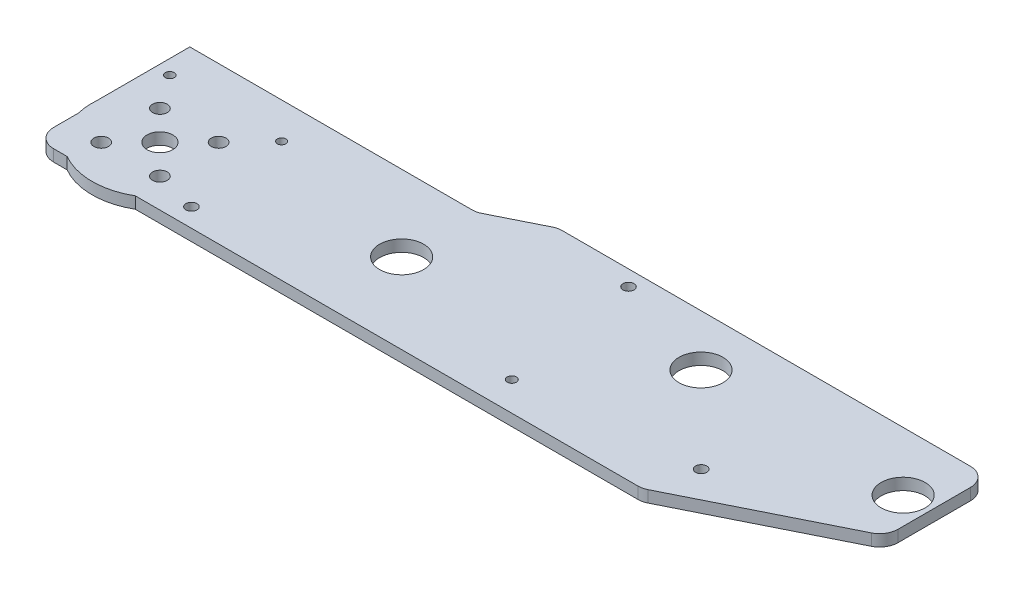
SolidWorks part; units mm, degrees
ref_plane "Front" through (0, 0, 0) normal (0, 0, 1) x (1, 0, 0)
ref_plane "Top" through (0, 0, 0) normal (0, 1, 0) x (1, 0, 0)
ref_plane "Right" through (0, 0, 0) normal (1, 0, 0) x (0, 0, -1)
sketch "Sketch1" plane through (0, 0, 0) normal (0, 1, 0) x (1, 0, 0)
  line L1 (0, 0) -> (210, 0)
  line L2 (0, 0) -> (0, -50)
  line L3 (0, -50) -> (210, -50)
  line L4 (210, 0) -> (210, -50)
  circle A7 centre (3.4895, -16.7877) radius 1.2117
  circle A8 centre (34.3726, -17.194) radius 1.1656
  circle A9 centre (37.5207, -44.9212) radius 1.5
  circle A10 centre (122, -42.0581) radius 1.25
  circle A12 centre (168.9752, -37.4032) radius 1.5173
  circle A13 centre (78.0103, -28.1) radius 3.4
  dimension "D1" = 210
  dimension "D2" = 50
extrude "Boss-Extrude1" add sketch "Sketch1" along normal blind 3.175
sketch "Sketch2" plane through (0, 3.175, 0) normal (0, 1, 0) x (1, 0, 0)
  line L0 (210, 0) -> (0, 0) construction
  line L1 (0, 0) -> (0, -50) construction
  circle A0 centre (10, -26) radius 2
  circle A1 centre (10, -42) radius 2
  circle A2 centre (26, -26) radius 2
  circle A3 centre (26, -42) radius 2
  dimension "D1" = 16
  dimension "D2" = 16
  dimension "D3" = 16
  dimension "D4" = 26
  dimension "D5" = 10
  dimension "D6" = 10
  dimension "D7" = 26
  dimension "D8" = 16
extrude "Cut-Extrude1" cut sketch "Sketch2" against normal blind 10
sketch "Sketch3" plane through (0, 3.175, 0) normal (0, 1, 0) x (1, 0, 0)
  line L0 (210, 0) -> (0, 0) construction
  line L1 (210, 0) -> (0, 0) construction
  circle A0 centre (78.0103, -28.1) radius 6
  circle A1 centre (145.5313, -14) radius 6
  circle A2 centre (18, -34) radius 0.587
  circle A3 centre (26, -26) radius 2 construction
  circle A4 centre (202.6463, -16) radius 6
  dimension "D1" = 28.1
  dimension "D3" = 16
  dimension "D4" = 14
  dimension "D7" = 125.222
  dimension "D2" = 60.2996
  dimension "D5" = 8
  dimension "D6" = 8
  dimension "D8" = 57.15
extrude "Cut-Extrude2" cut sketch "Sketch3" against normal blind 57.15
sketch "Sketch4" [suppressed] plane through (0, 3.175, 0) normal (0, 1, 0) x (1, 0, 0)
  line L0 (3.4895, -16.7877) -> (18, -34)
  line L1 (3.4895, -20.6627) -> (5.9498, -23.5811)
  line L2 (18, -34) -> (34.3726, -17.194)
  line L3 (34.3726, -17.194) -> (75.8499, -28.1)
  line L4 (75.8499, -28.1) -> (37.5207, -44.9212)
  line L5 (7.3432, -17.194) -> (9.8664, -20.303)
  circle A0 centre (18, -34) radius 15.9299
  circle A1 centre (3.4895, -16.7877) radius 3.8751
  circle A2 centre (34.3726, -17.194) radius 3.7227
  circle A3 centre (37.5207, -44.9212) radius 3.8676
  circle A4 centre (75.8499, -28.1) radius 12.797
  circle A5 centre (112.3021, -4.7393) radius 5.1588
  circle A6 centre (118.879, -40.0177) radius 4.9035
  circle A7 centre (140.772, -16) radius 12.6375
  circle A8 centre (168.9752, -37.4032) radius 4.2066
  circle A9 centre (197.922, -16) radius 12.8
sketch "Sketch5" [suppressed] plane through (0, 3.175, 0) normal (0, 1, 0) x (1, 0, 0)
  line L0 (210, 0) -> (0, 0) construction
  line L2 (-0.6266, -16.7877) -> (37.5207, -16.7877)
  line L3 (-0.6266, -16.7877) -> (-0.6266, -44.9212)
  line L4 (-0.6266, -44.9212) -> (37.5207, -44.9212)
  line L5 (37.5207, -16.7877) -> (37.5207, -44.9212)
  line L6 (75.8499, -15.182) -> (37.5207, -15.182)
  line L7 (75.8499, -15.182) -> (75.8499, -44.9212)
  line L8 (75.8499, -44.9212) -> (37.5207, -44.9212)
  line L9 (37.5207, -15.182) -> (37.5207, -44.9212)
  line L10 (112.3021, -4.7393) -> (75.8499, -4.7393)
  line L11 (112.3021, -4.7393) -> (112.3021, -44.9212)
  line L12 (112.3021, -44.9212) -> (75.8499, -44.9212)
  line L13 (75.8499, -4.7393) -> (75.8499, -44.9212)
  line L14 (112.3021, -4.7393) -> (102.3945, -4.7393)
  line L16 (112.3021, -4.7393) -> (112.3021, 0)
  line L17 (112.3021, 0) -> (102.3945, 0)
  line L18 (102.3945, -4.7393) -> (102.3945, 0)
  line L19 (210, -50) -> (210, 0) construction
  line L20 (112.3021, -4.7393) -> (123.1553, -4.7393)
  line L21 (112.3021, -4.7393) -> (112.3021, 0)
  line L22 (112.3021, 0) -> (123.1553, 0)
  line L23 (123.1553, -4.7393) -> (123.1553, 0)
  line L24 (112.3021, -4.7393) -> (140.772, -4.7393)
  line L25 (112.3021, -4.7393) -> (112.3021, -40.0177)
  line L26 (112.3021, -40.0177) -> (140.772, -40.0177)
  line L27 (140.772, -4.7393) -> (140.772, -40.0177)
  line L28 (140.772, -16) -> (168.9752, -16)
  line L29 (140.772, -16) -> (140.772, -40.0177)
  line L30 (140.772, -40.0177) -> (168.9752, -40.0177)
  line L31 (168.9752, -16) -> (168.9752, -40.0177)
  line L32 (168.9752, -4.7393) -> (210, -4.7393)
  line L33 (168.9752, -4.7393) -> (168.9752, -40.0177)
  line L34 (168.9752, -40.0177) -> (210, -40.0177)
  line L35 (210, -4.7393) -> (210, -40.0177)
  line L36 (0, -50) -> (210, -50) construction
  line L37 (160.7629, -40.0177) -> (177.2091, -40.0177)
  line L38 (160.7629, -40.0177) -> (160.7629, -44.9212)
  line L39 (160.7629, -44.9212) -> (177.2091, -44.9212)
  line L40 (177.2091, -40.0177) -> (177.2091, -44.9212)
  line L41 (112.3021, -40.0177) -> (126.3591, -40.0177)
  line L42 (112.3021, -40.0177) -> (112.3021, -47.7828)
  line L43 (112.3021, -47.7828) -> (126.3591, -47.7828)
  line L44 (126.3591, -40.0177) -> (126.3591, -47.7828)
  line L45 (30.5963, -44.9212) -> (44.6115, -44.9212)
  line L46 (30.5963, -44.9212) -> (30.5963, -50)
  line L47 (30.5963, -50) -> (44.6115, -50)
  line L48 (44.6115, -44.9212) -> (44.6115, -50)
  line L50 (-0.6266, -44.9212) -> (30.5963, -44.9212)
  line L51 (-0.6266, -44.9212) -> (-0.6266, -50)
  line L52 (-0.6266, -50) -> (30.5963, -50)
  line L53 (30.5963, -44.9212) -> (30.5963, -50)
  circle A0 centre (3.4895, -16.7877) radius 4.1161
  circle A1 centre (34.3726, -17.194) radius 3.8132
  circle A2 centre (75.8499, -28.1) radius 12.918
  circle A3 centre (112.3021, -4.7393) radius 5.2663
  circle A4 centre (140.772, -16) radius 13.0245
  circle A5 centre (197.922, -16) radius 12.3805
  circle A6 centre (168.9752, -37.4032) radius 4.7643
  circle A7 centre (118.879, -40.0177) radius 5.279
  circle A8 centre (37.5207, -44.9212) radius 4.2049
  line M12 (0, 0) -> (0, -50)
  line M13 (0, -50) -> (210, -50)
  line M14 (210, -50) -> (210, 0)
  line M15 (210, 0) -> (0, 0)
extrude "Cut-Extrude5" [suppressed] cut sketch "Sketch5" against normal blind 11.52 contours A5 L32 L23 L24 A4 L28 L33 M14 M15 | A1 L6 L13 L10 L18 A0 L2 M15 M12 | L8 L48 L34 L40 L39 L38 L30 L26 L44 L43 L42 L12 M13 M14
fillet "Fillet1" [suppressed] radius 5
sketch "Sketch10" plane through (0, 3.175, 0) normal (0, 1, 0) x (1, 0, 0)
  line L0 (210, -27.8594) -> (165.5029, -50)
  line L1 (210, -50) -> (210, 0) construction
  line L2 (0, -50) -> (210, -50) construction
  line L3 (165.5029, -50) -> (210, -50)
  line L4 (210, -50) -> (210, -27.8594)
  line L5 (92.5326, 0) -> (77.6548, -7.4028)
  line L6 (210, 0) -> (0, 0) construction
  line L7 (77.6548, -7.4028) -> (0, -7.4028)
  line L8 (0, 0) -> (0, -50) construction
  line L9 (0, -7.4028) -> (0, 0)
  line L10 (0, 0) -> (92.5326, 0)
extrude "Cut-Extrude7" cut sketch "Sketch10" against normal blind 10
fillet "Fillet3" radius 5 5 edges at (77.6548, 1.5875, 7.4028) (92.5326, 1.5875, 0) (210, 1.5875, 0) (210, 1.5875, 27.8594) (165.5029, 1.5875, 50)
sketch "Sketch11" plane through (0, 3.175, 0) normal (0, 1, 0) x (1, 0, 0)
  circle A0 centre (18, -34) radius 18.5
  circle A1 centre (10, -26) radius 2
  circle A2 centre (10, -42) radius 2
  circle A3 centre (26, -26) radius 2
  circle A4 centre (26, -42) radius 2
extrude "Boss-Extrude4" add sketch "Sketch11" against normal blind 3.175
sketch "Sketch16" plane through (0, 0, 7.4028) normal (0, 0, -1) x (-1, 0, 0)
  line L0 (0, 3.175) -> (-76.4796, 3.175) construction
  line L1 (0, 0) -> (-18.2576, 0)
  line L2 (0, 0) -> (0, 3.175)
  line L3 (0, 3.175) -> (-18.2576, 3.175)
  line L4 (-18.2576, 0) -> (-18.2576, 3.175)
extrude "Boss-Extrude7" add sketch "Sketch16" along normal blind 8.128
sketch "Sketch17" plane through (0, 0, 0) normal (-1, 0, 0) x (0, 0, 1)
  line L0 (-0.7252, 3.175) -> (29.728, 3.175) construction
  line L1 (-0.7252, 0) -> (32.5748, 0)
  line L2 (-0.7252, 0) -> (-0.7252, 3.175)
  line L3 (-0.7252, 3.175) -> (32.5748, 3.175)
  line L4 (32.5748, 0) -> (32.5748, 3.175)
  dimension "D1" = 33.3
extrude "Boss-Extrude8" add sketch "Sketch17" along normal blind 35.56
sketch "Sketch18" plane through (0, 3.175, 0) normal (0, 1, 0) x (1, 0, 0)
  line L0 (-35.56, 0.7252) -> (18.2576, 0.7252) construction
  circle A0 centre (-21.4859, -15.9248) radius 11.315
  circle A1 centre (-29.612, -23.7985) radius 2
  circle A2 centre (-29.3597, -7.7987) radius 2
  circle A3 centre (-13.3598, -8.0511) radius 2
  circle A4 centre (-13.6122, -24.0509) radius 2
  circle A5 centre (-21.4859, -15.9248) radius 4
  point P15 (-21.4859, -15.9248)
  dimension "D1" = 22.63
  dimension "D3" = 4
  dimension "D2" = 16.65
extrude "Cut-Extrude8" cut sketch "Sketch18" against normal blind 9 contours A2 | A1 | A4 | A3
sketch "Sketch19" plane through (0, 3.175, 0) normal (0, 1, 0) x (1, 0, 0)
  circle A0 centre (-21.3597, -15.7987) radius 4
  circle A1 centre (-29.3597, -7.7987) radius 2 construction
  dimension "D1" = 8
  dimension "D2" = 8
extrude "Cut-Extrude9" cut sketch "Sketch19" against normal blind 40
fillet "Fillet4" radius 5 4 edges at (0, 1.5875, 50) (18.2576, 1.5875, -0.7252) (-35.56, 1.5875, -0.7252) (-35.56, 1.5875, 32.5748)
sketch "Sketch20" plane through (0, 3.175, 0) normal (0, 1, 0) x (1, 0, 0)
  circle A0 centre (18, -34) radius 3.5
  circle A1 centre (10, -26) radius 2 construction
  dimension "D1" = 8
  dimension "D2" = 8
extrude "Cut-Extrude10" cut sketch "Sketch20" against normal blind 10
sketch "Sketch21" plane through (0, 3.175, 0) normal (0, 1, 0) x (1, 0, 0)
  line L0 (210, -24.7625) -> (210, -5) construction
  circle A0 centre (116, -4.2372) radius 1.5
  dimension "D1" = 94
extrude "Cut-Extrude11" cut sketch "Sketch21" against normal blind 10
sketch "Sketch22" plane through (0, 3.175, 0) normal (0, 1, 0) x (1, 0, 0)
  line L0 (18.2576, -4.2748) -> (18.2576, -7.4028) construction
  line L1 (-30.56, 0.7252) -> (13.2576, 0.7252) construction
  circle A0 centre (12.2576, -3.2748) radius 1.5
  dimension "D1" = 6
  dimension "D2" = 4
extrude "Cut-Extrude12" cut sketch "Sketch22" against normal blind 10
sketch "Sketch24" plane through (0, 3.175, 0) normal (0, 1, 0) x (1, 0, 0)
  line L0 (-30.56, 0.7252) -> (13.2576, 0.7252) construction
  line L1 (-35.56, -27.5748) -> (-35.56, -4.2748) construction
  circle A0 centre (-30.56, -15.7748) radius 1.5
  dimension "D1" = 16.5
  dimension "D2" = 5
extrude "Cut-Extrude13" cut sketch "Sketch24" against normal blind 10
sketch "Sketch25" plane through (0, 3.175, 0) normal (0, 1, 0) x (1, 0, 0)
  line L0 (18.2576, -7.4028) -> (76.4796, -7.4028) construction
  line L1 (-0.445, -32.5748) -> (-38.8525, -32.5748)
  line L2 (-0.445, -32.5748) -> (-0.445, 8.2536)
  line L3 (-0.445, 8.2536) -> (-38.8525, 8.2536)
  line L4 (-38.8525, -32.5748) -> (-38.8525, 8.2536)
  line L5 (-0.445, 8.2536) -> (19.7966, 8.2536)
  line L6 (-0.445, 8.2536) -> (-0.445, -7.4028)
  line L7 (-0.445, -7.4028) -> (19.7966, -7.4028)
  line L8 (19.7966, 8.2536) -> (19.7966, -7.4028)
  circle M1 centre (-30.56, -15.7748) radius 1.5
  circle M2 centre (12.2576, -3.2748) radius 1.5
  circle M5 centre (-21.3597, -15.7987) radius 4
  circle M6 centre (-13.3598, -8.0511) radius 2
  circle M7 centre (-13.6122, -24.0509) radius 2
  circle M8 centre (-29.612, -23.7985) radius 2
  circle M9 centre (-29.3597, -7.7987) radius 2
  line M24 (76.4796, -7.4028) -> (18.2576, -7.4028)
  line M25 (18.2576, -7.4028) -> (18.2576, -4.2748)
  arc M26 (18.2576, -4.2748) -> (13.2576, 0.7252) centre (13.2576, -4.2748) ccw
  line M27 (13.2576, 0.7252) -> (-30.56, 0.7252)
  arc M28 (-30.56, 0.7252) -> (-35.56, -4.2748) centre (-30.56, -4.2748) ccw
  line M29 (-35.56, -4.2748) -> (-35.56, -27.5748)
  arc M30 (-35.56, -27.5748) -> (-30.56, -32.5748) centre (-30.56, -27.5748) ccw
  line M31 (-30.56, -32.5748) -> (-0.445, -32.5748)
extrude "Cut-Extrude14" cut sketch "Sketch25" against normal blind 10 contours L2 M31 M27 M28 M29 M30 M1 M5 M7 M9 M8 M6 | L2 L7 M25 M26 M27 M2 | L8 L5 L2 M27 M26 M25 M24 | L4 L1 L2 L3 M30 M29 M28 M27 region at (-15.5025, 3.175, 32.0909) region at (-34.7063, 3.175, 32.0143) region at (8.4201, 3.175, 3.4553) region at (10.598, 3.175, -3.7605)
